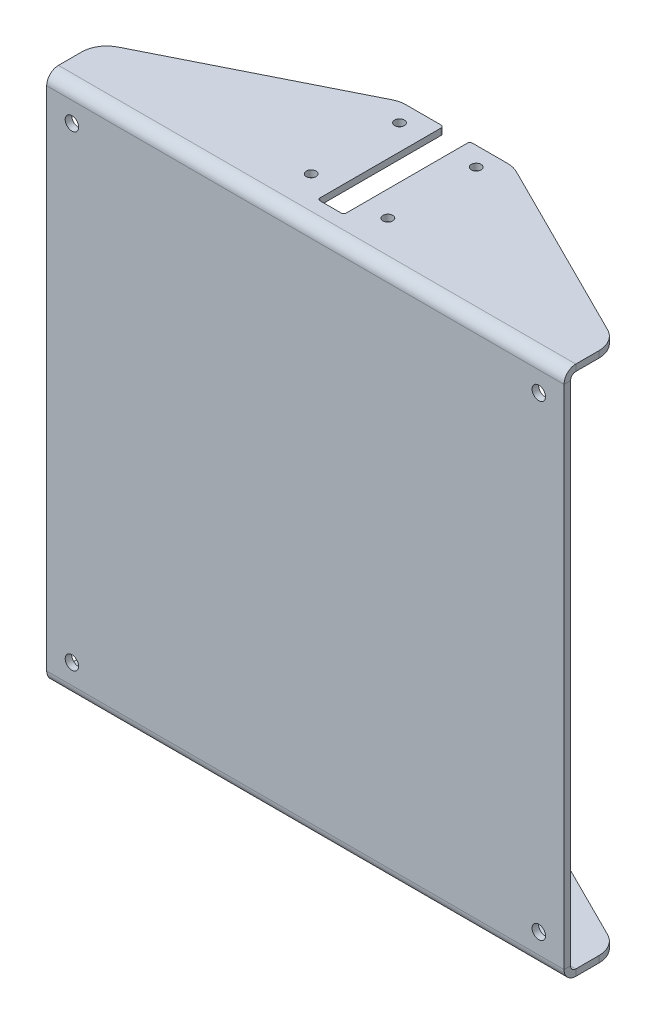
SolidWorks part; units mm, degrees
note: The reader was unsure of these and kept them because the rebuilt part matched: flange length of "Edge-Flange1".
material "5052-H32"
ref_plane "Front Plane" through (0, 0, 0) normal (0, 0, 1) x (1, 0, 0)
ref_plane "Top Plane" through (0, 0, 0) normal (0, 1, 0) x (1, 0, 0)
ref_plane "Right Plane" through (0, 0, 0) normal (1, 0, 0) x (0, 0, -1)
sketch "Sketch1" plane through (0, 0, 0) normal (0, 0, 1) x (1, 0, 0)
  line L1 (-130.175, -130.175) -> (130.175, -130.175)
  line L2 (-130.175, -130.175) -> (-130.175, 130.175)
  line L3 (-130.175, 130.175) -> (130.175, 130.175)
  line L4 (130.175, -130.175) -> (130.175, 130.175)
  line L5 (-130.175, -130.175) -> (130.175, 130.175) construction
  line L6 (-130.175, 130.175) -> (130.175, -130.175) construction
  point P0 (0, 0)
  dimension "D1" = 260.35
base flange "Base-Flange1" sketch "Sketch1" thickness 3.2639 reverse thickness direction no parameters "D1"=2.6568
edge flange "Edge-Flange1" sketch "Sketch14" flange profiles "Sketch14", "Sketch15" flange angle 90 flange length 76.2 flange position material outside bend radius 2.6568 thickness 3.2639 relief rectangular parameters "D6"=10, "D8"=1
sketch "Sketch14" plane through (0, 130.175, -3.2639) normal (0, -1, 0) x (-1, 0, 0)
  line L2 (-130.175, 0) -> (-130.175, 72.9361)
  line L3 (-130.175, 72.9361) -> (130.175, 72.9361)
  line L4 (130.175, 72.9361) -> (130.175, 0)
  line L5 (130.175, 0) -> (-130.175, 0) construction
  line L6 (130.175, 0) -> (-130.175, 0)
sketch "Sketch15" plane through (0, -130.175, -3.2639) normal (0, 1, 0) x (1, 0, 0)
  line L0 (130.175, 0) -> (-130.175, 0) construction
  line L1 (130.175, 0) -> (-130.175, 0)
  line L2 (130.175, 0) -> (130.175, 72.9361)
  line L3 (130.175, 72.9361) -> (-130.175, 72.9361)
  line L4 (-130.175, 72.9361) -> (-130.175, 0)
bend "EdgeBend1" bend radius 2.6568 bend angle 90 parameters "D5"=1
bend "EdgeBend2" bend radius 2.6568 bend angle 90 parameters "D5"=2
sketch "Sketch16" plane through (0, 133.4389, 0) normal (0, 1, 0) x (1, 0, 0)
  line L0 (-130.175, 76.2) -> (130.175, 76.2) construction
  line L1 (-6.604, 76.2) -> (6.604, 76.2)
  line L2 (-6.604, 76.2) -> (-6.604, 12.7)
  line L3 (-6.604, 12.7) -> (6.604, 12.7)
  line L4 (6.604, 76.2) -> (6.604, 12.7)
  point P6 (0, 12.7)
  dimension "D1" = 13.208
  dimension "D2" = 63.5
extrude "Cut-Extrude1" cut sketch "Sketch16" against normal through all normal cut yes
sketch "Sketch18" plane through (0, 133.4389, 0) normal (0, 1, 0) x (1, 0, 0)
  line L0 (-130.175, 76.2) -> (-130.175, 25.4)
  line L1 (-130.175, 5.9207) -> (-130.175, 76.2) construction
  line L2 (-130.175, 25.4) -> (-28.575, 76.2)
  line L3 (-28.575, 76.2) -> (-130.175, 76.2)
  line L4 (130.175, 76.2) -> (28.575, 76.2)
  line L5 (6.604, 76.2) -> (130.175, 76.2) construction
  line L6 (28.575, 76.2) -> (130.175, 25.4)
  line L7 (130.175, 76.2) -> (130.175, 5.9207) construction
  line L8 (130.175, 25.4) -> (130.175, 76.2)
  dimension "D1" = 50.8
  dimension "D2" = 101.6
  dimension "D3" = 21.971
extrude "Cut-Extrude2" cut sketch "Sketch18" against normal through all normal cut yes
fillet "Fillet1" radius 12.7 8 edges at (130.175, -131.807, -25.4) (130.175, 131.807, -25.4) (28.575, 131.807, -76.2) (-28.575, 131.807, -76.2) (-130.175, 131.807, -25.4) (28.575, -131.807, -76.2) (-28.575, -131.807, -76.2) (-130.175, -131.807, -25.4)
hole_wizard "#10 (0.1935) Diameter Hole1" positions "Sketch19" profile "Sketch20" hole size "#10" standard "ANSI Inch" end condition through all
sketch "Sketch19" plane through (0, 133.4389, 0) normal (0, 1, 0) x (1, 0, 0)
  line L0 (-6.604, 76.2) -> (-6.604, 12.7) construction
  line L1 (6.604, 12.7) -> (6.604, 76.2) construction
  line L2 (-25.5769, 76.2) -> (-6.604, 76.2) construction
  line L3 (-6.604, 12.7) -> (6.604, 12.7) construction
  point P0 (-19.304, 22.225)
  point P2 (-19.304, 66.675)
  point P4 (19.304, 66.675)
  point P6 (19.304, 22.225)
  dimension "D1" = 12.7
  dimension "D2" = 12.7
  dimension "D3" = 9.525
  dimension "D4" = 9.525
sketch "Sketch20" plane through (-19.304, 133.4389, -22.225) normal (1, 0, 0) x (0, 0, 1)
  line L0 (0, 0) -> (0, 266.8778)
  line L1 (0, 266.8778) -> (2.4574, 266.8778)
  line L2 (2.4574, 266.8778) -> (2.4574, 0)
  line L5 (2.4574, 0) -> (0, 0)
  line L11 (0, -6.35) -> (0, 107.95) construction
  dimension "Thru Hole Dia." = 4.9149
  dimension "Thru Hole Depth" = 266.8778
fillet "Fillet2" radius 1.27 8 edges at (6.604, 131.807, -76.2) (-6.604, 131.807, -76.2) (6.604, -131.807, -76.2) (-6.604, -131.807, -76.2) (6.604, -131.807, -12.7) (-6.604, -131.807, -12.7) (-6.604, 131.807, -12.7) (6.604, 131.807, -12.7)
hole_wizard "1/4 Clearance Hole1" positions "Sketch21" profile "Sketch22" hole size "1/4" standard "ANSI Inch" end condition through all
sketch "Sketch21" plane through (0, 0, 0) normal (0, 0, 1) x (1, 0, 0)
  line L1 (-117.475, -117.475) -> (117.475, -117.475) construction
  line L2 (-117.475, -117.475) -> (-117.475, 117.475) construction
  line L3 (-117.475, 117.475) -> (117.475, 117.475) construction
  line L4 (117.475, -117.475) -> (117.475, 117.475) construction
  line L5 (-117.475, -117.475) -> (117.475, 117.475) construction
  line L6 (-117.475, 117.475) -> (117.475, -117.475) construction
  point P3 (117.475, 117.475)
  point P132 (-117.475, -117.475)
  point P133 (-117.475, 117.475)
  point P134 (117.475, -117.475)
  point P147 (0, 0)
  dimension "D1" = 234.95
sketch "Sketch22" plane through (117.475, 117.475, 0) normal (1, 0, 0) x (0, -1, 0)
  line L0 (0, 0) -> (0, 76.2)
  line L1 (0, 76.2) -> (3.3782, 76.2)
  line L2 (3.3782, 76.2) -> (3.3782, 0)
  line L5 (3.3782, 0) -> (0, 0)
  line L11 (0, -6.35) -> (0, 107.95) construction
  dimension "Thru Hole Dia." = 6.7564
  dimension "Thru Hole Depth" = 76.2
sketch "Bend-Lines1" [suppressed] plane through (0, 0, 0) normal (0, 1, 0) x (1, 0, 0)
sketch "Bounding-Box1" [suppressed] plane through (0, 0, 0) normal (0, 1, 0) x (1, 0, 0)
sheet metal parameters "Sheet-Metal1" thickness 3.2639 parameters "D1"=2.6568
flat pattern "Flat-Pattern1" [suppressed]
sketch "Bend-Lines2" plane through (0, 0, 0) normal (0, 0, 1) x (1, 0, 0)
sketch3d "Bounding-Box2" [suppressed]
  line L0 (-130.175, -130.175, 0) -> (130.175, -130.175, 0) construction
  line L1 (-130.175, 130.175, 0) -> (130.175, 130.175, 0) construction
  line L2 (-130.175, -130.175, 0) -> (-130.175, 130.175, 0) construction
  line L3 (130.175, -130.175, 0) -> (130.175, 130.175, 0) construction
sheet metal parameters "Sheet-Metal2" thickness 3.2639 parameters "D1"=2.6568
flat pattern "Flat-Pattern1" [suppressed]
sketch "Bend-Lines2" plane through (0, 0, 0) normal (0, 0, 1) x (1, 0, 0)
  line L0 (-130.175, -127.6227) -> (130.175, -127.6227) construction
  line L1 (130.175, 127.6227) -> (-130.175, 127.6227) construction
  line L2 (-130.175, -127.6227) -> (130.175, -127.6227) construction
  line L3 (130.175, 127.6227) -> (-130.175, 127.6227) construction
sketch3d "Bounding-Box2" [suppressed]
  line L0 (130.175, 201.2703, 0) -> (130.175, -201.2703, 0) construction
  line L1 (-130.175, 201.2703, 0) -> (-130.175, -201.2703, 0) construction
  line L2 (130.175, 201.2703, 0) -> (-130.175, 201.2703, 0) construction
  line L3 (130.175, -201.2703, 0) -> (-130.175, -201.2703, 0) construction
bend of the flat pattern "Flatten-<EdgeBend1>1"
bend of the flat pattern "Flatten-<EdgeBend2>1"
sketch "Sketch16-1" [suppressed] plane through (0, 125.0703, 0) normal (0, 0, 1) x (1, 0, 0)
  line L1 (-6.35, 76.2) -> (6.35, 76.2)
  line L2 (-6.35, 76.2) -> (-6.35, 12.7)
  line L3 (-6.35, 12.7) -> (6.35, 12.7)
  line L4 (6.35, 76.2) -> (6.35, 12.7)
  dimension "D1" = 12.7
  dimension "D2" = 63.5
sheet metal parameters "Sheet-Metal4" thickness 3.2639 parameters "D1"=2.6568
flat pattern "Flat-Pattern1" [suppressed]
sketch "Bend-Lines2" plane through (0, 0, 0) normal (0, 0, 1) x (1, 0, 0)
  line L0 (-130.175, -127.6227) -> (130.175, -127.6227) construction
  line L1 (130.175, 127.6227) -> (-130.175, 127.6227) construction
  line L2 (-130.175, -127.6227) -> (130.175, -127.6227) construction
  line L3 (130.175, 127.6227) -> (-130.175, 127.6227) construction
sketch3d "Bounding-Box2" [suppressed]
  line L0 (130.175, 201.2703, 0) -> (130.175, -201.2703, 0) construction
  line L1 (-130.175, 201.2703, 0) -> (-130.175, -201.2703, 0) construction
  line L2 (130.175, 201.2703, 0) -> (-130.175, 201.2703, 0) construction
  line L3 (130.175, -201.2703, 0) -> (-130.175, -201.2703, 0) construction
bend of the flat pattern "Flatten-<EdgeBend1>1"
bend of the flat pattern "Flatten-<EdgeBend2>1"
sketch "Sketch16-1" [suppressed] plane through (0, 125.0703, 0) normal (0, 0, 1) x (1, 0, 0)
  line L1 (-6.35, 76.2) -> (6.35, 76.2)
  line L2 (-6.35, 76.2) -> (-6.35, 12.7)
  line L3 (-6.35, 12.7) -> (6.35, 12.7)
  line L4 (6.35, 76.2) -> (6.35, 12.7)
  dimension "D1" = 12.7
  dimension "D2" = 63.5
sheet metal parameters "Sheet-Metal5" thickness 3.2639 parameters "D1"=2.6568
flat pattern "Flat-Pattern1" [suppressed]
sketch "Bend-Lines2" plane through (0, 0, 0) normal (0, 0, 1) x (1, 0, 0)
  line L0 (-130.175, -127.6227) -> (130.175, -127.6227) construction
  line L1 (130.175, 127.6227) -> (-130.175, 127.6227) construction
  line L2 (-130.175, -127.6227) -> (130.175, -127.6227) construction
  line L3 (130.175, 127.6227) -> (-130.175, 127.6227) construction
sketch3d "Bounding-Box2" [suppressed]
  line L0 (130.175, -201.2703, 0) -> (130.175, 201.2703, 0) construction
  line L1 (-130.175, -201.2703, 0) -> (-130.175, 201.2703, 0) construction
  line L2 (130.175, -201.2703, 0) -> (-130.175, -201.2703, 0) construction
  line L3 (130.175, 201.2703, 0) -> (-130.175, 201.2703, 0) construction
bend of the flat pattern "Flatten-<EdgeBend1>1"
bend of the flat pattern "Flatten-<EdgeBend2>1"
sketch "Sketch16-1" [suppressed] plane through (0, 125.0703, 0) normal (0, 0, 1) x (1, 0, 0)
  line L1 (-6.35, 76.2) -> (6.35, 76.2)
  line L2 (-6.35, 76.2) -> (-6.35, 12.7)
  line L3 (-6.35, 12.7) -> (6.35, 12.7)
  line L4 (6.35, 76.2) -> (6.35, 12.7)
  dimension "D1" = 12.7
  dimension "D2" = 63.5
sheet metal parameters "Sheet-Metal6" thickness 3.2639 parameters "D1"=2.6568
flat pattern "Flat-Pattern1" [suppressed]
sketch "Bend-Lines2" plane through (0, 0, 0) normal (0, 0, 1) x (1, 0, 0)
  line L0 (-130.175, -127.6227) -> (130.175, -127.6227) construction
  line L1 (130.175, 127.6227) -> (-130.175, 127.6227) construction
  line L2 (-130.175, -127.6227) -> (130.175, -127.6227) construction
  line L3 (130.175, 127.6227) -> (-130.175, 127.6227) construction
sketch3d "Bounding-Box2" [suppressed]
  line L0 (130.175, -201.2703, 0) -> (130.175, 201.2703, 0) construction
  line L1 (-130.175, -201.2703, 0) -> (-130.175, 201.2703, 0) construction
  line L2 (130.175, -201.2703, 0) -> (-130.175, -201.2703, 0) construction
  line L3 (130.175, 201.2703, 0) -> (-130.175, 201.2703, 0) construction
bend of the flat pattern "Flatten-<EdgeBend1>1"
bend of the flat pattern "Flatten-<EdgeBend2>1"
sketch "Sketch16-1" plane through (0, 125.0703, 0) normal (0, 0, 1) x (1, 0, 0)
  line L1 (-6.35, 76.2) -> (6.35, 76.2)
  line L2 (-6.35, 76.2) -> (-6.35, 12.7)
  line L3 (-6.35, 12.7) -> (6.35, 12.7)
  line L4 (6.35, 76.2) -> (6.35, 12.7)
  dimension "D1" = 12.7
  dimension "D2" = 63.5
sheet metal parameters "Sheet-Metal7" thickness 3.2639 parameters "D1"=2.6568
flat pattern "Flat-Pattern1" [suppressed]
sketch "Bend-Lines2" plane through (0, 0, 0) normal (0, 0, 1) x (1, 0, 0)
  line L0 (-130.175, -130.8866) -> (130.175, -130.8866) construction
  line L1 (130.175, 130.8866) -> (-130.175, 130.8866) construction
  line L2 (-130.175, -130.8866) -> (130.175, -130.8866) construction
  line L3 (130.175, 130.8866) -> (-130.175, 130.8866) construction
sketch3d "Bounding-Box2" [suppressed]
  line L0 (130.175, -204.5342, 0) -> (130.175, 204.5342, 0) construction
  line L1 (-130.175, -204.5342, 0) -> (-130.175, 204.5342, 0) construction
  line L2 (130.175, -204.5342, 0) -> (-130.175, -204.5342, 0) construction
  line L3 (130.175, 204.5342, 0) -> (-130.175, 204.5342, 0) construction
bend of the flat pattern "Flatten-<EdgeBend1>1"
bend of the flat pattern "Flatten-<EdgeBend2>1"
sketch "Sketch16-1" plane through (0, 128.3342, 0) normal (0, 0, 1) x (1, 0, 0)
  line L1 (-6.604, 76.2) -> (6.604, 76.2)
  line L2 (-6.604, 76.2) -> (-6.604, 12.7)
  line L3 (-6.604, 12.7) -> (6.604, 12.7)
  line L4 (6.604, 76.2) -> (6.604, 12.7)
  dimension "D1" = 13.208
  dimension "D2" = 63.5
